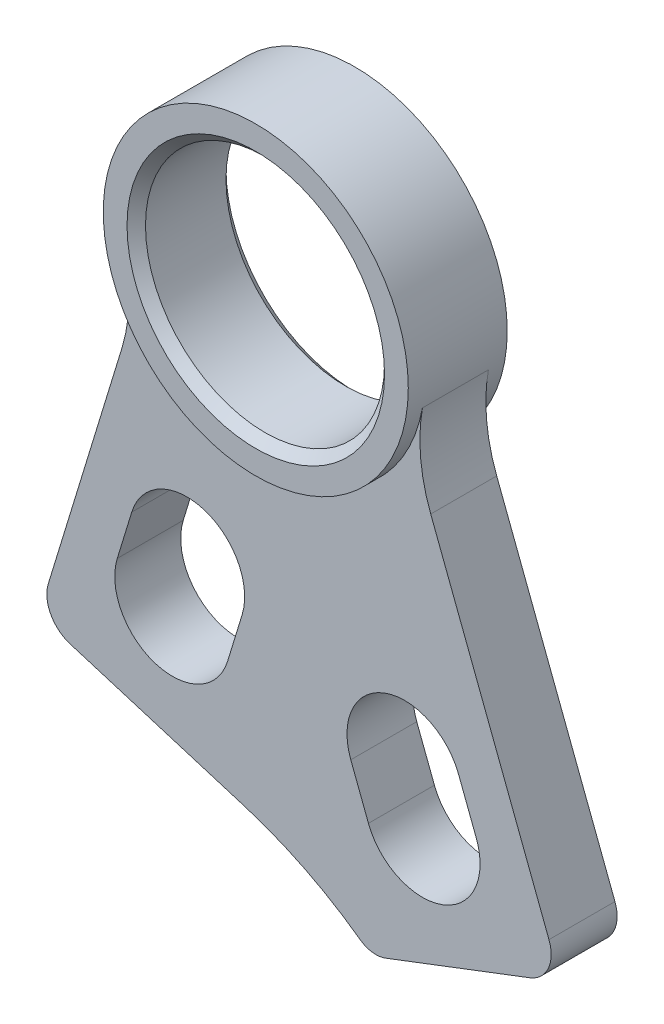
SolidWorks part; units mm, degrees
material "AISI 4130 Steel, annealed at 865C"
ref_plane "X-Y Datum" through (0, 0, 0) normal (0, 0, 1) x (1, 0, 0)
ref_plane "X-Z Datum" through (0, 0, 0) normal (0, 1, 0) x (1, 0, 0)
ref_plane "Y-Z Datum" through (0, 0, 0) normal (1, 0, 0) x (0, 0, -1)
sketch "Sketch1" plane through (0, 0, 0) normal (0, 0, 1) x (1, 0, 0)
  line L0 (-9.6066, -31.4257) -> (-8.2143, -26.8713) construction
  line L1 (-14.9201, -29.8014) -> (-13.5278, -25.247)
  line L2 (-4.293, -33.05) -> (-2.9008, -28.4956)
  line L3 (14.4495, -37.8146) -> (12.7495, -33.3658) construction
  line L4 (9.2592, -39.7979) -> (7.5593, -35.3491)
  line L5 (19.6397, -35.8313) -> (17.9398, -31.3826)
  line L6 (-14.4677, -12.0304) -> (-22.4911, -38.2771)
  line L7 (-22.4911, -38.2771) -> (-2.7551, -44.3102)
  line L10 (8.4937, -51.1368) -> (27.7717, -43.7704)
  line L11 (27.7717, -43.7704) -> (15.2553, -11.0146)
  line L12 (0, 0) -> (127, -332.3615) construction
  line L14 (-11.2309, -36.7392) -> (-12.6231, -41.2937) construction
  line L15 (16.4328, -43.0048) -> (18.1327, -47.4536) construction
  line L16 (18.7898, -33.6069) -> (23.2385, -31.907) construction
  line L17 (-14.224, -27.5242) -> (-18.7784, -26.1319) construction
  line L18 (-15.0657, -13.9867) -> (4.6702, -20.0198) construction
  line L19 (4.6702, -20.0198) -> (-2.7551, -44.3102) construction
  line L20 (-3.5969, -30.7728) -> (0.9575, -32.165) construction
  line L21 (-6.59, -21.5577) -> (-5.1978, -17.0033) construction
  line L22 (8.4937, -51.1368) -> (-0.5727, -27.41) construction
  line L23 (-0.5727, -27.41) -> (18.7054, -20.0436) construction
  line L24 (8.4093, -37.5735) -> (3.9605, -39.2734) construction
  line L25 (10.7663, -28.1756) -> (9.0663, -23.7268) construction
  line L28 (-101.6, -332.3615) -> (0, 0) construction
  circle A0 centre (0, 0) radius 11.5062
  arc A1 (-14.9201, -29.8014) -> (-4.293, -33.05) centre (-9.6066, -31.4257) ccw
  arc A2 (-2.9008, -28.4956) -> (-13.5278, -25.247) centre (-8.2143, -26.8713) ccw
  arc A3 (9.2592, -39.7979) -> (19.6397, -35.8313) centre (14.4495, -37.8146) ccw
  arc A4 (17.9398, -31.3826) -> (7.5593, -35.3491) centre (12.7495, -33.3658) ccw
  arc A5 (14.4546, -2.5696) -> (-14.2454, -3.5504) centre (0, 0) ccw
  arc A6 (15.2553, -11.0146) -> (14.4546, -2.5696) centre (30.0845, -5.3482) cw
  arc A7 (-14.4677, -12.0304) -> (-14.2454, -3.5504) centre (-29.6492, -7.3896) ccw
  arc A10 (10.8964, -50.2187) -> (7.5756, -48.7341) centre (9.9783, -47.816) cw
  circle A12 centre (9.9783, -47.816) radius 2.5722 construction
  arc A14 (-14.2454, -3.5504) -> (14.4546, -2.5696) centre (0, 0) ccw
  arc A15 (-2.7551, -44.3102) -> (8.4686, -49.8985) centre (-13.8932, -80.7459) cw
  point P5 (-8.9104, -29.1485)
  point P11 (13.5995, -35.5902)
  point P24 (18.1327, -47.4536)
  point P31 (-12.6231, -41.2937)
  point P39 (16.4328, -43.0048)
  dimension "D1" = 23.0124
  dimension "D2" = 3.175
  dimension "D8" = 15.875
  dimension "D6" = 38.1
  dimension "D3" = 20.6375
  dimension "D4" = 4.7625
  dimension "D5" = 25.4
extrude "Boss-Extrude2" add sketch "Sketch1" along normal mid plane 9.525 contours A5 A14 A0 region at (-0.4873, 14.2576, 0)
extrude "Boss-Extrude3" add sketch "Sketch1<4>" along normal mid plane 6.35 contours A14 A7 L6 L7 A10 L10 L11 A6 A4 L5 A3 L4 A2 L2 A1 L1 region at (2.9485, -29.2125, 0)
sketch "Sketch1<4>" plane through (0, 0, 0) normal (0, 0, 1) x (1, 0, 0) same geometry as "Sketch1"
fillet "Fillet1" radius 3.175 2 edges at (-22.4911, -38.2771, 0) (27.7717, -43.7704, 0)
chamfer "Chamfer1" distance 0.889 angle 45 2 edges at (11.5062, 0, -4.7625) (11.5062, 0, 4.7625)
fillet "Fillet2" [suppressed] radius 1.27
